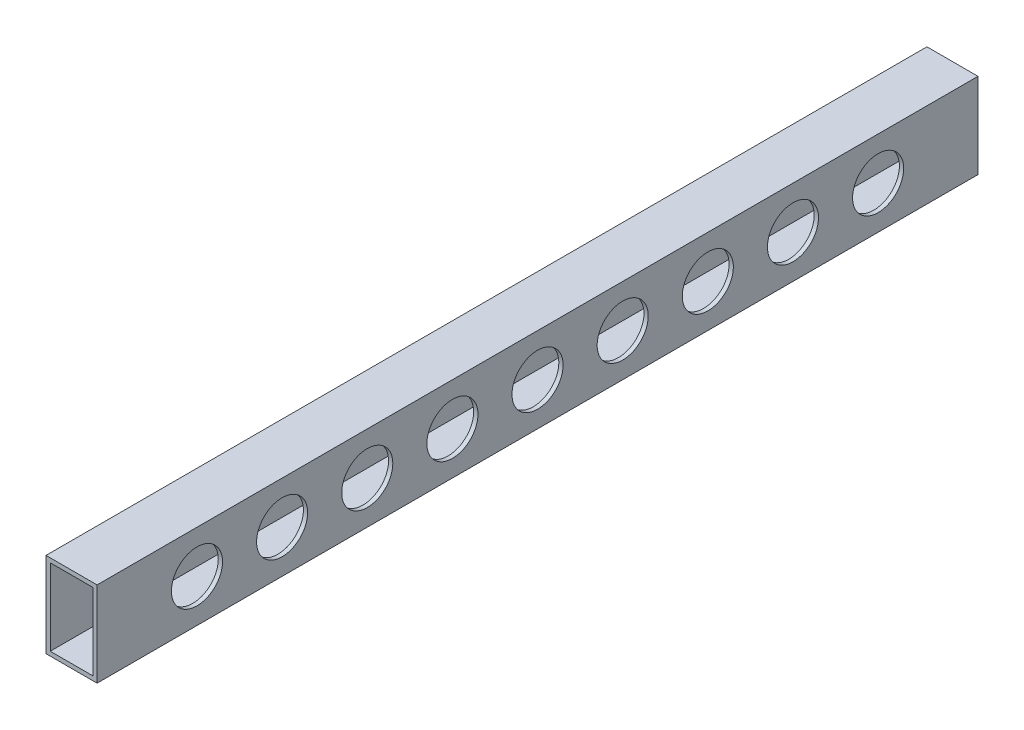
SolidWorks part; units mm, degrees
ref_plane "Front Plane" through (0, 0, 0) normal (0, 0, 1) x (1, 0, 0)
ref_plane "Top Plane" through (0, 0, 0) normal (0, 1, 0) x (1, 0, 0)
ref_plane "Right Plane" through (0, 0, 0) normal (1, 0, 0) x (0, 0, -1)
sketch "Sketch1" plane through (0, 0, 0) normal (0, 0, 1) x (1, 0, 0)
  line L1 (-19.05, -31.75) -> (19.05, -31.75)
  line L2 (-19.05, -31.75) -> (-19.05, 31.75)
  line L3 (-19.05, 31.75) -> (19.05, 31.75)
  line L4 (19.05, -31.75) -> (19.05, 31.75)
  line L5 (-19.05, -31.75) -> (19.05, 31.75) construction
  line L6 (-19.05, 31.75) -> (19.05, -31.75) construction
  line L7 (-15.875, -28.575) -> (15.875, -28.575)
  line L8 (-15.875, -28.575) -> (-15.875, 28.575)
  line L9 (-15.875, 28.575) -> (15.875, 28.575)
  line L10 (15.875, -28.575) -> (15.875, 28.575)
  line L11 (-15.875, -28.575) -> (15.875, 28.575) construction
  line L12 (-15.875, 28.575) -> (15.875, -28.575) construction
  point P0 (0, 0)
  point P1 (0, 0)
  point P7 (0, 0)
  dimension "D1" = 38.1
  dimension "D2" = 63.5
  dimension "D3" = 3.175
  dimension "D4" = 3.175
extrude "Boss-Extrude1" add sketch "Sketch1" along normal blind 656.9964
sketch "Sketch2" plane through (19.05, 0, 0) normal (1, 0, 0) x (0, 0, -1)
  line L1 (-656.9964, -31.75) -> (-656.9964, 31.75) construction
  circle A0 centre (-582.4982, 0) radius 19.05
  circle A1 centre (-518.9982, 0) radius 19.05
  circle A2 centre (-455.4982, 0) radius 19.05
  circle A3 centre (-391.9982, 0) radius 19.05
  circle A4 centre (-328.4982, 0) radius 19.05
  circle A5 centre (-264.9982, 0) radius 19.05
  circle A6 centre (-201.4982, 0) radius 19.05
  circle A7 centre (-137.9982, 0) radius 19.05
  circle A8 centre (-74.4982, 0) radius 19.05
  point P7 (0, 0)
  point P8 (0, 0)
  point P25 (0, 0)
  dimension "D1" = 38.1
  dimension "D2" = 74.4982
  dimension "D3" = 9
extrude "Cut-Extrude1" cut sketch "Sketch2" against normal up to surface (38.1 mm away) up to face at (-19.05, 0, 328.4982)
